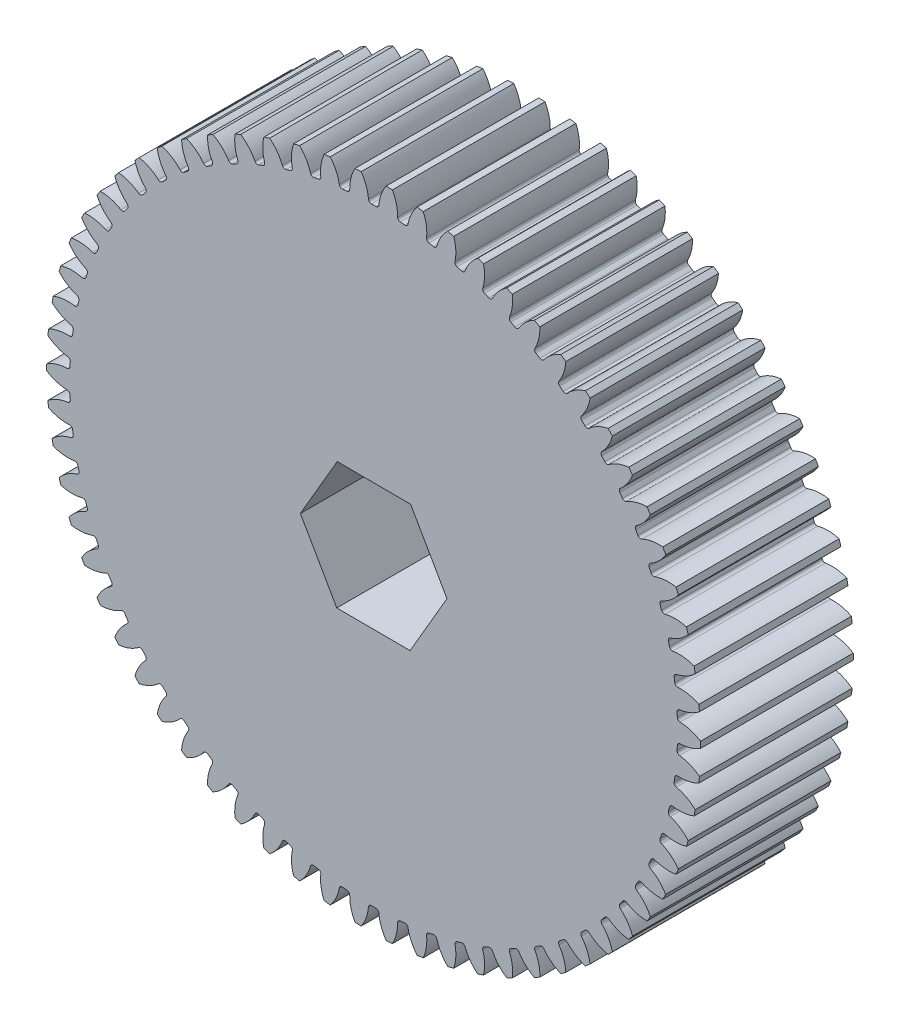
SolidWorks part; units mm, degrees
material "ABS"
ref_plane "Front Plane" through (0, 0, 0) normal (0, 0, 1) x (1, 0, 0)
ref_plane "Top Plane" through (0, 0, 0) normal (0, 1, 0) x (1, 0, 0)
ref_plane "Right Plane" through (0, 0, 0) normal (1, 0, 0) x (0, 0, -1)
sketch "Sketch1" plane through (0, 0, 0) normal (0, 0, 1) x (1, 0, 0)
  circle A0 centre (0, 0) radius 33
  circle A2 centre (0, 0) radius 34
  circle A3 centre (0, 0) radius 31.6
  dimension "D1" = 66
  dimension "D2" = 68
  dimension "D3" = 2.4
extrude "Boss-Extrude1" add sketch "Sketch1" along normal blind 12.7 and the other way blind 3.175 contours A2
sketch "Sketch3" plane through (0, 0, -3.175) normal (0, 0, -1) x (-1, 0, 0)
  line L0 (0, 0) -> (0, 34) construction
  line L1 (-0.7853, 32.9907) -> (0.7853, 32.9907) construction
  line L2 (0, 0) -> (-0.5273, 31.5956) construction
  line L3 (0, 30.833) -> (-1.5049, 34.9676) construction
  line L4 (0, 0) -> (1.6178, 33.9615) construction
  line L5 (0.7853, 32.9907) -> (2.3542, 32.9159) construction
  circle A0 centre (0, 0) radius 34 construction
  arc A1 (-2.2098, 34.9302) -> (-0.5273, 31.5956) centre (-4.8148, 31.524) cw
  arc A2 (2.2098, 34.9302) -> (0.5273, 31.5956) centre (4.8148, 31.524) ccw
  circle A3 centre (0, 0) radius 31.6 construction
  arc A4 (0.5273, 31.5956) -> (-0.5273, 31.5956) centre (0, 0) ccw
  arc A5 (2.2098, 34.9302) -> (-2.2098, 34.9302) centre (0, 0) ccw
  circle A6 centre (0, 0) radius 33 construction
  circle A8 centre (0, 0) radius 33 construction
  dimension "D1" = 1
  dimension "D2" = 20
  dimension "D3" = 2.727
extrude "Cut-Extrude2" cut sketch "Sketch3" against normal blind 20
fillet "Fillet2" radius 0.3 2 edges at (-0.5273, 31.5956, 4.7625) (0.5273, 31.5956, 4.7625)
pattern_circular "CirPattern2" count 66 over 360 about axis through (0, 0, -3.175) along (0, 0, 1) of "Cut-Extrude2", "Fillet2" reverse direction yes
sketch "Sketch4" plane through (0, 0, 12.7) normal (0, 0, 1) x (1, 0, 0)
  line L1 (3.8362, 6.5904) -> (-3.7894, 6.6175)
  line L2 (-3.7894, 6.6175) -> (-7.6256, 0.027)
  line L3 (-7.6256, 0.027) -> (-3.8362, -6.5904)
  line L4 (-3.8362, -6.5904) -> (3.7894, -6.6175)
  line L5 (3.7894, -6.6175) -> (7.6256, -0.027)
  line L6 (7.6256, -0.027) -> (3.8362, 6.5904)
  circle A0 centre (0, 0) radius 6.604 construction
  dimension "D1" = 13.208
extrude "Cut-Extrude3" cut sketch "Sketch4" against normal blind 10
equation "\"Module\"= 1mm"
equation "\"Number of Teeth\"= 66"
equation "\"D1@Sketch1\"=\"Module\"*\"Number of Teeth\""
equation "\"D2@Sketch1\"=(\"Number of Teeth\"+2) * \"Module\""
equation "\"D3@Sketch3\"=180 /\"Number of Teeth\" "
equation "\"D1@Fillet2\"=.3 * \"Module\""
equation "\"D1@CirPattern2\"=\"Number of Teeth\""
equation "\"D3@Sketch1\"=\"Module\"*if( \"Module\"=>1.25,2.25,2.4)"
